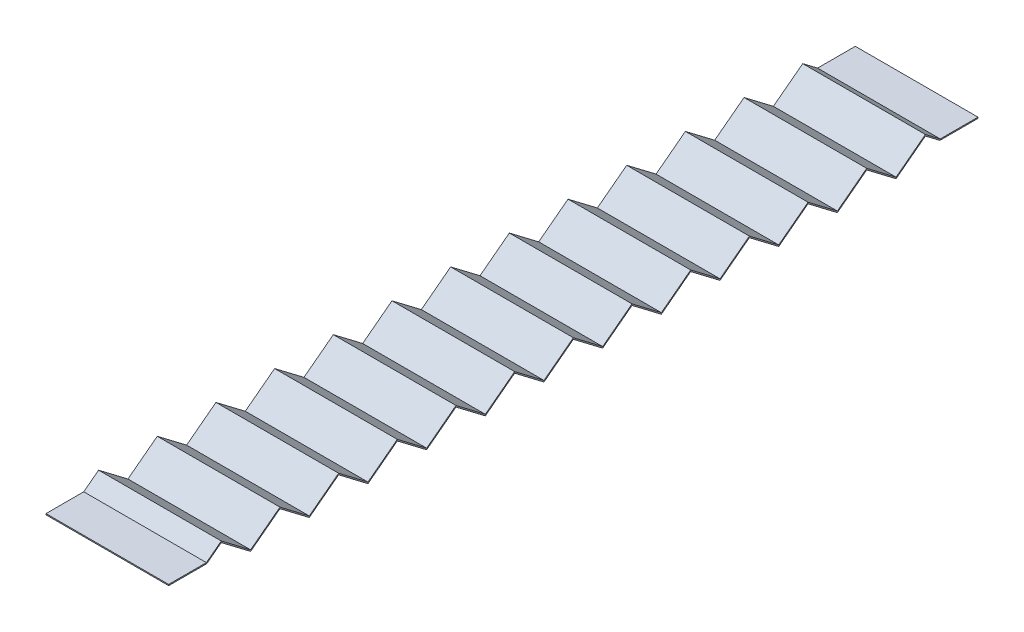
SolidWorks part; units mm, degrees
ref_plane "Front Plane" through (0, 0, 0) normal (0, 0, 1) x (1, 0, 0)
ref_plane "Top Plane" through (0, 0, 0) normal (0, 1, 0) x (1, 0, 0)
ref_plane "Right Plane" through (0, 0, 0) normal (1, 0, 0) x (0, 0, -1)
sketch "Sketch2" plane through (0, 0, 0) normal (0, 0, 1) x (1, 0, 0)
  line L1 (-27.5, 10) -> (27.5, 10)
  line L2 (-27.5, 10) -> (-27.5, 0)
  line L3 (-27.5, 0) -> (27.5, 0)
  line L4 (27.5, 10) -> (27.5, 0)
  point P4 (0, 0)
  dimension "D1" = 10
  dimension "D2" = 55
sketch "Sketch3" plane through (0, 0, 0) normal (1, 0, 0) x (0, 0, -1)
  line L0 (0, 10) -> (362.8226, 10) construction
  line L1 (0, 0) -> (362.8226, 0) construction
  line L2 (362.8226, 4.75) -> (362.8226, 22.75) construction
  line L3 (17, 5) -> (23.5765, 10)
  line L4 (23.5765, 10) -> (36.7294, 0)
  line L5 (36.7294, 0) -> (49.8823, 10)
  line L6 (49.8823, 10) -> (63.0352, 0)
  line L7 (63.0352, 0) -> (76.1881, 10)
  line L8 (76.1881, 10) -> (89.341, 0)
  line L9 (89.341, 0) -> (102.4939, 10)
  line L10 (102.4939, 10) -> (115.6468, 0)
  line L11 (115.6468, 0) -> (128.7997, 10)
  line L12 (128.7997, 10) -> (141.9526, 0)
  line L13 (141.9526, 0) -> (155.1055, 10)
  line L14 (155.1055, 10) -> (168.2584, 0)
  line L15 (168.2584, 0) -> (181.4113, 10)
  line L16 (181.4113, 10) -> (194.5642, 0)
  line L17 (194.5642, 0) -> (207.7171, 10)
  line L18 (207.7171, 10) -> (220.87, 0)
  line L19 (0, 10) -> (0, 0) construction
  line L20 (220.87, 0) -> (234.0229, 10)
  line L21 (234.0229, 10) -> (247.1758, 0)
  line L22 (247.1758, 0) -> (260.3287, 10)
  line L23 (260.3287, 10) -> (273.4816, 0)
  line L24 (273.4816, 0) -> (286.6345, 10)
  line L25 (286.6345, 10) -> (299.7874, 0)
  line L26 (299.7874, 0) -> (312.9403, 10)
  line L27 (312.9403, 10) -> (326.0933, 0)
  line L28 (326.0933, 0) -> (339.2462, 10)
  line L29 (339.2462, 10) -> (345.8226, 5)
  line L30 (362.8226, 10) -> (362.8226, 0) construction
  line L31 (17, 5) -> (0, 5)
  line L32 (345.8226, 5) -> (362.8226, 5)
  dimension "D2" = 17
  dimension "D1" = 10
  dimension "D3" = 17
extrude "Extrude-Thin1" add sketch "Sketch3" against normal mid plane 55 thin thin type mid plane wall 0.5
